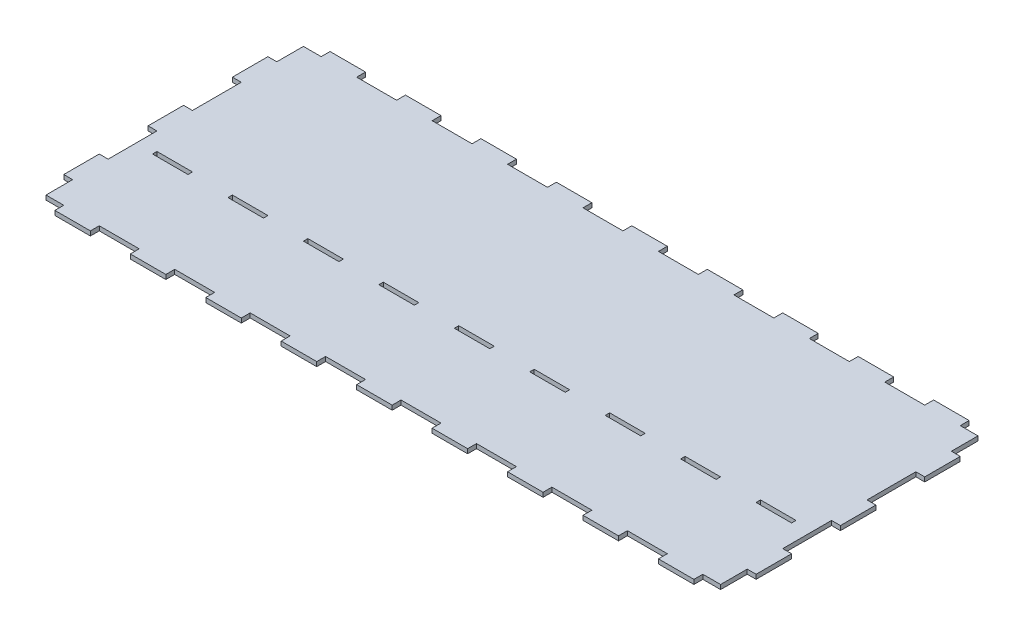
SolidWorks part; units mm, degrees
material "Mahogany"
ref_plane "Front" through (0, 0, 0) normal (0, 0, 1) x (1, 0, 0)
ref_plane "Top" through (0, 0, 0) normal (0, 1, 0) x (1, 0, 0)
ref_plane "Right" through (0, 0, 0) normal (1, 0, 0) x (0, 0, -1)
sketch "Sketch1" plane through (0, 0, 0) normal (0, 1, 0) x (1, 0, 0)
  line L0 (-190, -72.5) -> (-190, 72.5) construction
  line L1 (-195, -77.5) -> (195, -77.5) construction
  line L2 (-195, -77.5) -> (-195, 77.5) construction
  line L3 (-195, 77.5) -> (195, 77.5) construction
  line L4 (195, -77.5) -> (195, 77.5) construction
  line L5 (-195, -77.5) -> (195, 77.5) construction
  line L6 (-195, 77.5) -> (195, -77.5) construction
  line L7 (-190, 72.5) -> (190, 72.5) construction
  line L8 (190, -72.5) -> (190, 72.5) construction
  line L9 (-190, -72.5) -> (190, -72.5) construction
  line L10 (0, -22.2716) -> (0, 23.3858) construction
  line L11 (-34.4066, 0) -> (32.6527, 0) construction
  line L12 (-180, -72.5) -> (-180, -77.5)
  line L13 (-180, 72.5) -> (-160, 72.5) construction
  line L14 (-180, 72.5) -> (-180, 77.5)
  line L15 (-180, 77.5) -> (-160, 77.5)
  line L16 (-160, 72.5) -> (-160, 77.5)
  line L17 (-180, 72.5) -> (-160, 77.5) construction
  line L18 (-180, 77.5) -> (-160, 72.5) construction
  line L19 (-190, 57.5) -> (-195, 57.5)
  line L20 (-190, 57.5) -> (-190, 37.5) construction
  line L21 (-190, 37.5) -> (-195, 37.5)
  line L22 (-195, 57.5) -> (-195, 37.5)
  line L23 (-190, 57.5) -> (-195, 37.5) construction
  line L24 (-190, 37.5) -> (-195, 57.5) construction
  line L25 (-180, -77.5) -> (-160, -77.5)
  line L26 (-160, -72.5) -> (-160, -77.5)
  line L27 (190, 37.5) -> (195, 37.5)
  line L28 (195, 57.5) -> (195, 37.5)
  line L29 (190, 57.5) -> (195, 57.5)
  line L30 (-117.5, 72.5) -> (-117.5, 77.5)
  line L31 (-137.5, 77.5) -> (-117.5, 77.5)
  line L32 (-137.5, 72.5) -> (-137.5, 77.5)
  line L33 (-137.5, -72.5) -> (-137.5, -77.5)
  line L34 (-137.5, -77.5) -> (-117.5, -77.5)
  line L35 (-117.5, -72.5) -> (-117.5, -77.5)
  line L36 (-75, 72.5) -> (-75, 77.5)
  line L37 (-95, 77.5) -> (-75, 77.5)
  line L38 (-95, 72.5) -> (-95, 77.5)
  line L39 (-95, -72.5) -> (-95, -77.5)
  line L40 (-95, -77.5) -> (-75, -77.5)
  line L41 (-75, -72.5) -> (-75, -77.5)
  line L42 (-32.5, 72.5) -> (-32.5, 77.5)
  line L43 (-52.5, 77.5) -> (-32.5, 77.5)
  line L44 (-52.5, 72.5) -> (-52.5, 77.5)
  line L45 (-52.5, -72.5) -> (-52.5, -77.5)
  line L46 (-52.5, -77.5) -> (-32.5, -77.5)
  line L47 (-32.5, -72.5) -> (-32.5, -77.5)
  line L48 (10, 72.5) -> (10, 77.5)
  line L49 (-10, 77.5) -> (10, 77.5)
  line L50 (-10, 72.5) -> (-10, 77.5)
  line L51 (-10, -72.5) -> (-10, -77.5)
  line L52 (-10, -77.5) -> (10, -77.5)
  line L53 (10, -72.5) -> (10, -77.5)
  line L54 (52.5, 72.5) -> (52.5, 77.5)
  line L55 (32.5, 77.5) -> (52.5, 77.5)
  line L56 (32.5, 72.5) -> (32.5, 77.5)
  line L57 (32.5, -72.5) -> (32.5, -77.5)
  line L58 (32.5, -77.5) -> (52.5, -77.5)
  line L59 (52.5, -72.5) -> (52.5, -77.5)
  line L60 (95, 72.5) -> (95, 77.5)
  line L61 (75, 77.5) -> (95, 77.5)
  line L62 (75, 72.5) -> (75, 77.5)
  line L63 (75, -72.5) -> (75, -77.5)
  line L64 (75, -77.5) -> (95, -77.5)
  line L65 (95, -72.5) -> (95, -77.5)
  line L66 (137.5, 72.5) -> (137.5, 77.5)
  line L67 (117.5, 77.5) -> (137.5, 77.5)
  line L68 (117.5, 72.5) -> (117.5, 77.5)
  line L69 (117.5, -72.5) -> (117.5, -77.5)
  line L70 (117.5, -77.5) -> (137.5, -77.5)
  line L71 (137.5, -72.5) -> (137.5, -77.5)
  line L72 (180, 72.5) -> (180, 77.5)
  line L73 (160, 77.5) -> (180, 77.5)
  line L74 (160, 72.5) -> (160, 77.5)
  line L75 (160, -72.5) -> (160, -77.5)
  line L76 (160, -77.5) -> (180, -77.5)
  line L77 (180, -72.5) -> (180, -77.5)
  line L78 (190, 10) -> (195, 10)
  line L79 (195, 10) -> (195, -10)
  line L80 (190, -10) -> (195, -10)
  line L81 (-190, 10) -> (-195, 10)
  line L82 (-195, 10) -> (-195, -10)
  line L83 (-190, -10) -> (-195, -10)
  line L84 (190, -37.5) -> (195, -37.5)
  line L85 (195, -37.5) -> (195, -57.5)
  line L86 (190, -57.5) -> (195, -57.5)
  line L87 (-190, -37.5) -> (-195, -37.5)
  line L88 (-195, -37.5) -> (-195, -57.5)
  line L89 (-190, -57.5) -> (-195, -57.5)
  line L90 (-190, 57.5) -> (-190, 72.5)
  line L91 (-190, 72.5) -> (-180, 72.5)
  line L92 (-190, -57.5) -> (-190, -72.5)
  line L93 (-190, -72.5) -> (-180, -72.5)
  line L94 (180, -72.5) -> (190, -72.5)
  line L95 (190, -72.5) -> (190, -57.5)
  line L96 (180, 72.5) -> (190, 72.5)
  line L97 (190, 72.5) -> (190, 57.5)
  line L98 (160, 72.5) -> (137.5, 72.5)
  line L99 (160, -72.5) -> (137.5, -72.5)
  line L100 (117.5, -72.5) -> (95, -72.5)
  line L101 (117.5, 72.5) -> (95, 72.5)
  line L102 (75, -72.5) -> (52.5, -72.5)
  line L103 (75, 72.5) -> (52.5, 72.5)
  line L104 (32.5, -72.5) -> (10, -72.5)
  line L105 (32.5, 72.5) -> (10, 72.5)
  line L106 (-10, -72.5) -> (-32.5, -72.5)
  line L107 (-10, 72.5) -> (-32.5, 72.5)
  line L108 (-52.5, -72.5) -> (-75, -72.5)
  line L109 (-52.5, 72.5) -> (-75, 72.5)
  line L110 (-95, -72.5) -> (-117.5, -72.5)
  line L111 (-95, 72.5) -> (-117.5, 72.5)
  line L112 (-137.5, -72.5) -> (-160, -72.5)
  line L113 (-137.5, 72.5) -> (-160, 72.5)
  line L114 (-190, 37.5) -> (-190, 10)
  line L115 (-190, -10) -> (-190, -37.5)
  line L116 (-180, 72.5) -> (-202.5, 72.5) [skipped]
  line L117 (-180, -72.5) -> (-202.5, -72.5) [skipped]
  line L118 (190, -10) -> (190, -37.5)
  line L119 (190, 37.5) -> (190, 10)
  line L120 (-137.5, -22.5) -> (-137.5, -20)
  line L121 (-180, -22.5) -> (-160, -22.5)
  line L122 (-180, -22.5) -> (-180, -20)
  line L123 (-180, -20) -> (-160, -20)
  line L124 (-160, -22.5) -> (-160, -20)
  line L125 (-180, -22.5) -> (-160, -20) construction
  line L126 (-180, -20) -> (-160, -22.5) construction
  line L127 (-137.5, -22.5) -> (-117.5, -22.5)
  line L128 (-117.5, -22.5) -> (-117.5, -20)
  line L129 (-137.5, -20) -> (-117.5, -20)
  line L130 (-95, -22.5) -> (-95, -20)
  line L131 (-95, -22.5) -> (-75, -22.5)
  line L132 (-75, -22.5) -> (-75, -20)
  line L133 (-95, -20) -> (-75, -20)
  line L134 (-52.5, -22.5) -> (-52.5, -20)
  line L135 (-52.5, -22.5) -> (-32.5, -22.5)
  line L136 (-32.5, -22.5) -> (-32.5, -20)
  line L137 (-52.5, -20) -> (-32.5, -20)
  line L138 (-10, -22.5) -> (-10, -20)
  line L139 (-10, -22.5) -> (10, -22.5)
  line L140 (10, -22.5) -> (10, -20)
  line L141 (-10, -20) -> (10, -20)
  line L142 (32.5, -22.5) -> (32.5, -20)
  line L143 (32.5, -22.5) -> (52.5, -22.5)
  line L144 (52.5, -22.5) -> (52.5, -20)
  line L145 (32.5, -20) -> (52.5, -20)
  line L146 (75, -22.5) -> (75, -20)
  line L147 (75, -22.5) -> (95, -22.5)
  line L148 (95, -22.5) -> (95, -20)
  line L149 (75, -20) -> (95, -20)
  line L150 (117.5, -22.5) -> (117.5, -20)
  line L151 (117.5, -22.5) -> (137.5, -22.5)
  line L152 (137.5, -22.5) -> (137.5, -20)
  line L153 (117.5, -20) -> (137.5, -20)
  line L154 (160, -22.5) -> (160, -20)
  line L155 (160, -22.5) -> (180, -22.5)
  line L156 (180, -22.5) -> (180, -20)
  line L157 (160, -20) -> (180, -20)
  circle A0 centre (-55, 0) radius 2.5
  circle A1 centre (55, 0) radius 2.5
  point P0 (0, 0)
  point P18 (-170, 75)
  point P23 (-192.5, 47.5)
  point P116 (-170, -21.25)
  dimension "D15" = 5
  dimension "D1" = 390
  dimension "D2" = 155
  dimension "D4" = 20
  dimension "D5" = 15
  dimension "D6" = 20
  dimension "D9" = 20
  dimension "D10" = 15
  dimension "D11" = 9
  dimension "D12" = 55
  dimension "D13" = 2.5
  dimension "D16" = 110
  dimension "D3" = 5
  dimension "D7" = 9
  dimension "D8" = 3
  dimension "D14" = 9
extrude "Boss-Extrude1" [suppressed] add sketch "Sketch1" along normal blind 2.5
extrude "Boss-Extrude2" add sketch "Sketch1<2>" along normal blind 2.5 contours L119 L27 L28 L29 L97 L96 L72 L73 L74 L98 L66 L67 L68 L101 L60 L61 L62 L103 L54 L55 L56 L105 L48 L49 L50 L107 L42 L43 L44 L109 L36 L37 L38 L111 L30 L31 L32 L113 L16 L15 L14 L91 L90 L19 L22 L21 L114 L81 L82 L83 L115 | A0 | A1 region at (0, 0, -0.1677) region at (-55, 0, 0) region at (55, 0, 0)
sketch "Sketch1<2>" plane through (0, 0, 0) normal (0, 1, 0) x (1, 0, 0) same geometry as "Sketch1"
